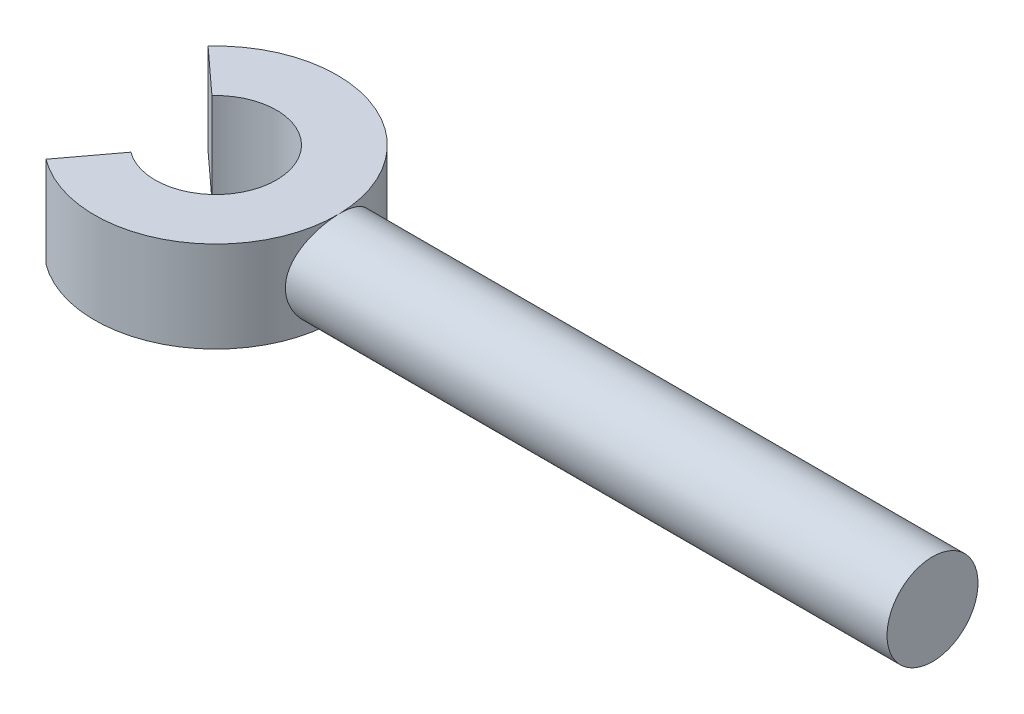
SolidWorks part; units mm, degrees
ref_plane "Front Plane" through (0, 0, 0) normal (0, 0, 1) x (1, 0, 0)
ref_plane "Top Plane" through (0, 0, 0) normal (0, 1, 0) x (1, 0, 0)
ref_plane "Right Plane" through (0, 0, 0) normal (1, 0, 0) x (0, 0, -1)
sketch "Sketch1" plane through (0, 0, 0) normal (1, 0, 0) x (0, 0, -1)
  circle A0 centre (0, 0) radius 0.75
  dimension "D1" = 1.5
extrude "Boss-Extrude1" add sketch "Sketch1" along normal blind 10
sketch "Sketch7" plane through (0, 0, 0) normal (0, 1, 0) x (1, 0, 0)
  line L0 (-2.5244, 0.6438) -> (-3.2626, 1.3184)
  line L1 (-2.385, -0.8318) -> (-2.9837, -1.6327)
  arc A0 (-3.2626, 1.3184) -> (-2.9837, -1.6327) centre (-1.7862, -0.0308) cw
  arc A1 (-2.5244, 0.6438) -> (-2.385, -0.8318) centre (-1.7862, -0.0308) cw
  dimension "D1" = 2
  dimension "D2" = 1
extrude "Boss-Extrude2" add sketch "Sketch7" along normal blind 0.75 and the other way blind 0.75
